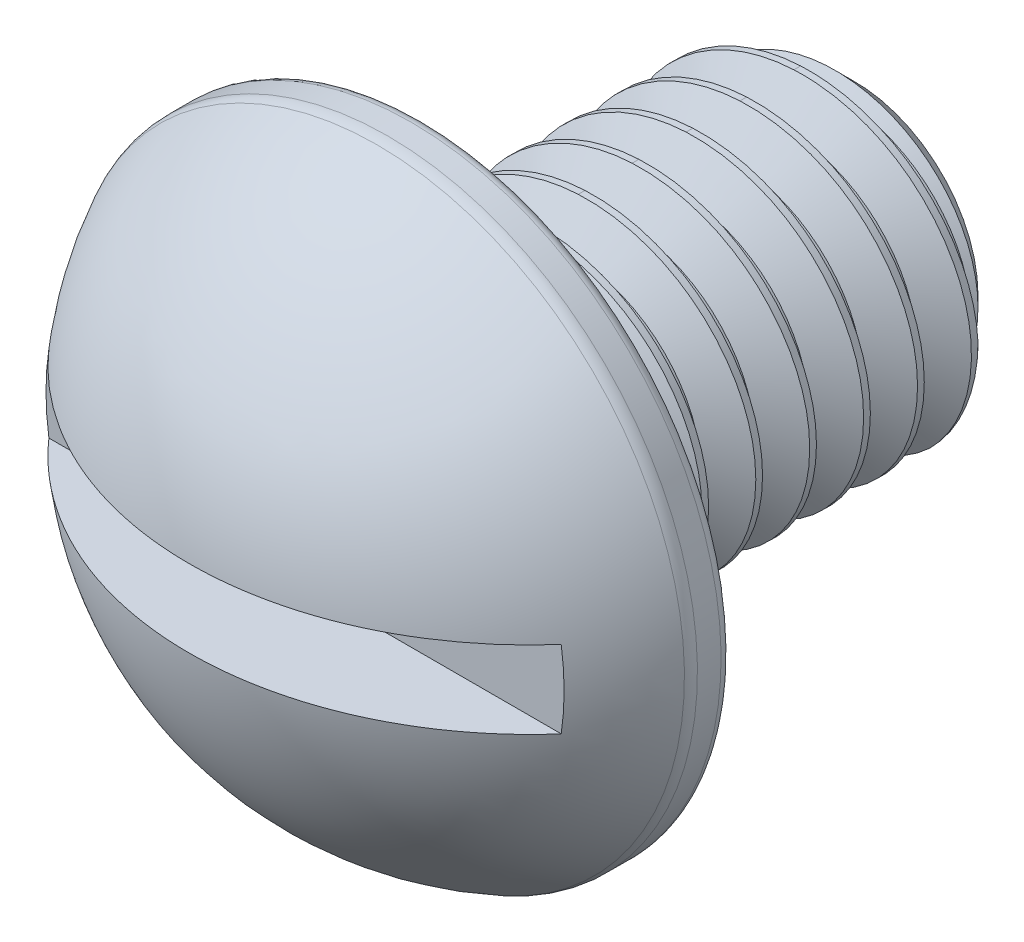
SolidWorks part; units mm, degrees
ref_plane "Front" through (0, 0, 0) normal (0, 0, 1) x (1, 0, 0)
ref_plane "Top" through (0, 0, 0) normal (0, 1, 0) x (1, 0, 0)
ref_plane "Right" through (0, 0, 0) normal (1, 0, 0) x (0, 0, -1)
sketch "Sketch1" plane through (0, 0, 0) normal (0, 0, 1) x (1, 0, 0)
  circle A0 centre (0, 0) radius 4.5593
  dimension "Head Dia" = 9.1186
extrude "Extrude3" add sketch "Sketch1" along normal blind 3.4798
sketch "Sketch11" plane through (0, 0, 0) normal (1, 0, 0) x (0, 0, -1)
  line L0 (0, 0) -> (-3.7338, 0) construction
  line L4 (-3.4798, 4.5593) -> (-3.4798, -4.5593) construction
  line L5 (-3.7338, 5.2972) -> (0, 5.2972)
  line L7 (0, 5.2972) -> (0, 4.3853)
  line L8 (-0.522, 4.5593) -> (-0.174, 4.5593)
  line L9 (0, -4.5593) -> (0, 4.5593) construction
  line L11 (0, 4.5593) -> (-3.4798, 4.5593) construction
  line L13 (-3.4798, 0) -> (-3.7338, 0)
  line L14 (-3.7338, 0) -> (-3.7338, 5.2972)
  arc A0 (-0.6768, 4.5229) -> (-3.4798, 0) centre (1.5709, 0) ccw
  arc A1 (-0.174, 4.5593) -> (0, 4.3853) centre (-0.174, 4.3853) cw
  arc A2 (-0.6768, 4.5229) -> (-0.522, 4.5593) centre (-0.522, 4.2113) cw
  dimension "D2" = 0.174
  dimension "D4" = 0.348
  dimension "D3" = 0.254
  dimension "D1" = 0.348
  dimension "D5" = 0.9119
revolve "Cut-Revolve3" cut sketch "Sketch11" angle 360 about L0
sketch "Sketch4" plane through (0, 0, 0) normal (1, 0, 0) x (0, 0, -1)
  line L0 (0, 0) -> (6.35, 0)
  line L3 (6.35, 0) -> (6.35, 2.413)
  line L4 (6.35, 2.413) -> (0, 2.413)
  line L6 (0, 2.413) -> (0, 0)
  line L9 (6.35, 2.413) -> (6.35, -2.413) construction
  dimension "length" = 6.35
  dimension "dia" = 4.826
revolve "Revolve1" add sketch "Sketch4" angle 360 about L0
chamfer "Chamfer1" distance 0.5953 angle 45 1 edges at (2.413, 0, -6.35)
sketch "Sketch13" plane through (0, 0, -6.35) normal (0, 0, -1) x (-1, 0, 0)
  circle A2 centre (0, 0) radius 2.413
curve "Helix/Spiral1" pitch 0.7937 height 7.1437 turns 9
sketch "Sketch14" plane through (0, 0, 0) normal (1, 0, 0) x (0, 0, -1)
  line L0 (6.35, 2.413) -> (7.0445, 2.413)
  line L1 (7.0445, 2.413) -> (6.7469, 1.8974)
  line L2 (6.7469, 1.8974) -> (6.6477, 1.8974)
  line L3 (6.6477, 1.8974) -> (6.35, 2.413)
  line L4 (6.4988, 2.1552) -> (6.8957, 2.1552) construction
  dimension "D1" = 0.0992
  dimension "D2" = 60
  dimension "D3" = 0.3969
sweep "Cut-Sweep1" cut profiles "Sketch14" path "Helix/Spiral1"
ref_plane "Plane1" through (0, 0, 31.75) normal (0, 0, -1) x (-1, 0, 0)
sketch "Sketch22" plane through (0, 0, 0) normal (0, 1, 0) x (1, 0, 0)
  line L0 (0, 6.35) -> (0, 0) construction
  line L1 (0, 6.35) -> (0, 0)
split line "Split Line1"
sketch "Sketch29" [suppressed] plane through (0, 0, -31.75) normal (0, 0, -1) x (-1, 0, 0)
  circle A0 centre (0, 0) radius 3.175 construction
  circle A1 centre (0, 0) radius 3.175
  point P3 (0, -3.175)
extrude "Extrude11" [suppressed] add sketch "Sketch29" against normal up to surface (31.75 mm away)
sketch "Sketch26" plane through (0, 0, 0) normal (0, 0, 1) x (1, 0, 0)
  circle A1 centre (0, 0) radius 0.5461
  dimension "D1" = 1.0922
extrude "Extrude13" [suppressed] add sketch "Sketch26" along normal up to vertex
ref_plane "Plane2" through (0, 0, 3.4798) normal (0, 0, 1) x (1, 0, 0)
sketch "Sketch30" plane through (0, 0, 3.4798) normal (0, 0, 1) x (1, 0, 0)
  line L0 (-4.5593, 0.5699) -> (4.5593, -0.5699) construction
  line L1 (-4.5593, 0.5699) -> (4.5593, 0.5699)
  line L2 (-4.5593, 0.5699) -> (-4.5593, -0.5699)
  line L3 (-4.5593, -0.5699) -> (4.5593, -0.5699)
  line L4 (4.5593, 0.5699) -> (4.5593, -0.5699)
  circle A0 centre (0, 0) radius 4.5593 construction
  dimension "D1" = 1.1398
extrude "Extrude12" cut sketch "Sketch30" against normal blind 1.7399
sketch "Sketch18" plane through (0, 0, 0) normal (1, 0, 0) x (0, 0, -1)
  line L1 (6.35, 2.413) -> (0, 2.413) construction
  point P0 (4.445, -2.413)
  point P1 (4.445, 2.413)
  point P2 (-3.4798, 0.5699)
  dimension "D1" = 1.905
equation "\"D3@Helix/Spiral1\" = \"length@Sketch4\" + \"D4@Helix/Spiral1\""
equation "\"D1@Sketch14\" = \"D4@Helix/Spiral1\" * .125"
equation "\"D3@Sketch14\" = \"D4@Helix/Spiral1\" * .5"
equation "\"D1@Sketch11\" = \"Head Ht@Extrude3\" / 10"
equation "\"D2@Sketch11\" = \"D1@Sketch11\" / 2"
equation "\"D4@Sketch11\" = \"D1@Sketch11\""
equation "\"D5@Sketch11\" = \"Head Dia@Sketch1\" / 10"
equation "\"D1@Sketch30\" = \"Head Dia@Sketch1\" / 8"
equation "\"D1@Extrude12\" = \"Head Ht@Extrude3\" / 2"
equation "\"D1@Chamfer1\" = \"D4@Helix/Spiral1\" * .75"
